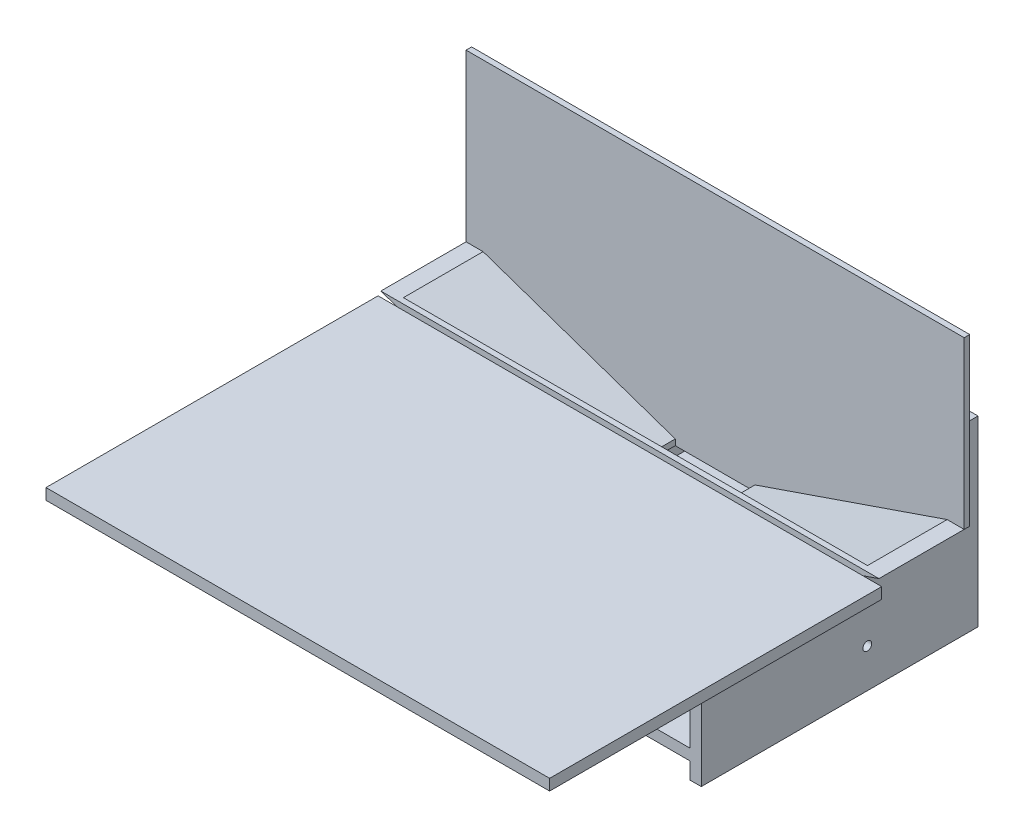
SolidWorks part; units mm, degrees
ref_plane "前基準面" through (0, 0, 0) normal (0, 0, 1) x (1, 0, 0)
ref_plane "上基準面" through (0, 0, 0) normal (0, 1, 0) x (1, 0, 0)
ref_plane "右基準面" through (0, 0, 0) normal (1, 0, 0) x (0, 0, -1)
sketch "草圖4" plane through (0, 0, 0) normal (0, 1, 0) x (1, 0, 0)
  line L1 (-127.5, 125) -> (127.5, 125)
  line L2 (-127.5, 125) -> (-127.5, -125)
  line L3 (-127.5, -125) -> (127.5, -125)
  line L4 (127.5, 125) -> (127.5, -125)
  line L5 (-127.5, 125) -> (127.5, -125) construction
  line L6 (-127.5, -125) -> (127.5, 125) construction
  point P0 (0, 0)
  dimension "D1" = 255
  dimension "D2" = 250
extrude "填料-伸長2" add sketch "草圖4" along normal blind 10
sketch "草圖7" plane through (0, 10, 0) normal (0, 1, 0) x (1, 0, 0)
  line L0 (-127.5, -125) -> (127.5, -125) construction
  line L1 (-127.5, 125) -> (-117.5, 125)
  line L2 (-127.5, 125) -> (-127.5, -125)
  line L3 (-127.5, -125) -> (-117.5, -125)
  line L4 (-117.5, 125) -> (-117.5, -125)
  line L5 (127.5, 125) -> (-127.5, 125) construction
  line L6 (127.5, -125) -> (117.5, -125)
  line L7 (127.5, -125) -> (127.5, 125)
  line L8 (127.5, 125) -> (117.5, 125)
  line L9 (117.5, -125) -> (117.5, 125)
  line L10 (0, 160.1697) -> (0, -166.2631) construction
  line L20 (42.5, -150) -> (-42.5, -150) construction
  line L21 (42.5, -150) -> (42.5, 110) construction
  line L22 (42.5, 110) -> (-42.5, 110) construction
  line L23 (-42.5, -150) -> (-42.5, 110) construction
  dimension "D1" = 10
  dimension "D2" = 10
  dimension "D4" = 260
  dimension "D5" = 85
extrude "填料-伸長3" add sketch "草圖7" along normal blind 140 and the other way blind 25
sketch "草圖9" plane through (-127.5, 0, 0) normal (-1, 0, 0) x (0, 0, 1)
  line L0 (-125, 0) -> (125, 0) construction
  line L2 (-125, 150) -> (-125, -15) construction
  circle A0 centre (-25, 20) radius 4
  dimension "D1" = 8
  dimension "D2" = 20
  dimension "D3" = 100
extrude "除料-伸長1" cut sketch "草圖9" against normal up to next
mirror "鏡射1" about plane through (0, 0, 0) normal (1, 0, 0) of "除料-伸長1"
sketch "草圖12" plane through (0, 10, 0) normal (0, 1, 0) x (1, 0, 0)
  line L0 (0, 132.8422) -> (0, -180.4749) construction
  line L1 (-117.5, -125) -> (117.5, -125) construction
  line L2 (8, -7.5) -> (-8, -7.5)
  line L3 (38, -60) -> (-38, -60) construction
  line L4 (38, -60) -> (38, 20) construction
  line L5 (38, 20) -> (-38, 20) construction
  line L6 (-38, -60) -> (-38, 20) construction
  line L7 (7.5, 20) -> (-7.5, 20) construction
  line L8 (7.5, 20) -> (7.5, 35) construction
  line L9 (7.5, 35) -> (-7.5, 35) construction
  line L10 (-7.5, 20) -> (-7.5, 35) construction
  line L15 (8, -7.5) -> (8, 62.5)
  line L16 (8, 62.5) -> (-8, 62.5)
  line L17 (-8, -7.5) -> (-8, 62.5)
  circle A0 centre (-62.5, -95) radius 42.5
  circle A1 centre (62.5, -95) radius 42.5
  circle A2 centre (0, -55) radius 35
  point P7 (20, -95)
  point P12 (-20, -95)
  point P13 (0, -60)
  point P18 (0, -90)
  point P23 (0, 35)
  point P24 (7.5, 27.5)
  point P25 (-8, 27.5)
  point P26 (0, -7.5)
  point P27 (0, 0)
  dimension "D1" = 85
  dimension "D3" = 40
  dimension "D6" = 70
  dimension "D2" = 30
  dimension "D4" = 80
  dimension "D5" = 76
  dimension "D7" = 30
  dimension "D8" = 65
  dimension "D9" = 15
  dimension "D10" = 15
  dimension "D11" = 70
  dimension "D12" = 16
sketch "草圖14" plane through (0, 150, 0) normal (0, 1, 0) x (1, 0, 0)
  line L0 (-127.5, 125) -> (-127.5, -125) construction
  line L1 (-127.5, 20) -> (127.5, 20)
  line L2 (-127.5, 20) -> (-127.5, 25)
  line L3 (-127.5, 25) -> (127.5, 25)
  line L4 (127.5, 20) -> (127.5, 25)
  line L5 (127.5, -125) -> (127.5, 125) construction
  line L6 (38, 20) -> (-38, 20) construction
  dimension "D1" = 5
extrude "填料-伸長6" add sketch "草圖14" against normal blind 50
sketch "草圖15" plane through (0, 0, -20) normal (0, 0, 1) x (1, 0, 0)
  line L0 (0, 0) -> (0, 160.4698) construction
  line L1 (-36, 100) -> (36, 100) construction
  line L2 (-117.5, 100) -> (117.5, 100) construction
  line L12 (-36, 100) -> (-225, 165)
  line L13 (-225, 165) -> (225, 165)
  line L14 (225, 165) -> (36, 100)
  line L15 (36, 100) -> (-36, 100)
  point P7 (0, 100)
  dimension "D1" = 72
  dimension "D2" = 65
  dimension "D3" = 450
extrude "填料-伸長7" add sketch "草圖15" along normal blind 82
ref_plane "平面1" through (0, 0, 57) normal (0, 0, 1) x (1, 0, 0)
sketch "草圖16" plane through (0, 0, 57) normal (0, 0, 1) x (1, 0, 0)
  line L10 (225, 165) -> (-225, 165) construction
  line L11 (209.6258, 165) -> (-209.6258, 165)
  line L12 (-36, 105.2874) -> (-36, 100)
  line L13 (-36, 100) -> (36, 100)
  line L14 (36, 100) -> (36, 105.2874)
  line L15 (0, 0) -> (0, 183.6441) construction
  line L16 (-36, 100) -> (36, 100) construction
  line L20 (-112.5, 155) -> (-112.5, 131.597)
  line L21 (-112.5, 131.597) -> (-35.1642, 105)
  line L22 (-35.1642, 105) -> (35.1642, 105)
  line L23 (35.1642, 105) -> (112.5, 131.597)
  line L24 (112.5, 131.597) -> (112.5, 155)
  line L25 (195.0873, 160) -> (-195.0873, 160)
  line L39 (112.5, 155) -> (132.5, 155)
  line L41 (132.5, 138.4753) -> (195.0873, 160)
  line L42 (36, 105.2874) -> (209.6258, 165)
  line L43 (-195.0873, 160) -> (-132.5, 138.4753)
  line L44 (-209.6258, 165) -> (-36, 105.2874)
  line L45 (-132.5, 155) -> (-112.5, 155)
  line L47 (-132.5, 138.4753) -> (-132.5, 155)
  line L49 (132.5, 155) -> (132.5, 138.4753)
  point P11 (34.9393, 105.1611)
  point P16 (101.8703, 143.8038)
  dimension "D2" = 72
  dimension "D1" = 5
extrude "除料-伸長2" cut sketch "草圖16" against normal blind 72
sketch "草圖17" plane through (0, 150, 0) normal (0, 1, 0) x (1, 0, 0)
  line L0 (225, -62) -> (-225, -62) construction
  line L1 (-227.5, -62) -> (227.5, -62)
  line L2 (-227.5, -62) -> (-227.5, -362)
  line L3 (-227.5, -362) -> (227.5, -362)
  line L4 (227.5, -62) -> (227.5, -362)
  line L5 (0, 132.8422) -> (0, -180.4749) construction
  line L6 (0, 132.8422) -> (0, -180.4749) construction
  line L7 (-50, -62) -> (-50, -462) construction
  line L8 (-200, -62) -> (-100, -62) construction
  line L9 (-200, -62) -> (-200, -462) construction
  line L10 (-200, -462) -> (-100, -462) construction
  line L11 (-100, -62) -> (-100, -462) construction
  line L12 (-50, -62) -> (50, -62) construction
  line L13 (50, -62) -> (50, -462) construction
  line L14 (-50, -462) -> (50, -462) construction
  line L15 (100, -62) -> (100, -462) construction
  line L16 (100, -62) -> (200, -62) construction
  line L17 (200, -62) -> (200, -462) construction
  line L18 (100, -462) -> (200, -462) construction
  point P8 (0, -362)
  point P13 (0, -462)
  dimension "D1" = 100
  dimension "D2" = 400
  dimension "D4" = 50
  dimension "D5" = 455
  dimension "D6" = 300
  dimension "D3" = 3
extrude "填料-伸長8" add sketch "草圖17" along normal blind 10
sketch "草圖18" plane through (0, 165, 0) normal (0, 1, 0) x (1, 0, 0)
  line L0 (225, 20) -> (-225, 20) construction
  line L1 (225, 20) -> (-225, 20)
  line L2 (225, 20) -> (225, 15)
  line L3 (225, -62) -> (225, 20) construction
  line L4 (225, 15) -> (-225, 15)
  line L5 (-225, -62) -> (-225, 20) construction
  line L6 (-225, 15) -> (-225, 20)
  line L7 (209.6258, 15) -> (-209.6258, 15) construction
extrude "填料-伸長9" add sketch "草圖18" along normal blind 150
